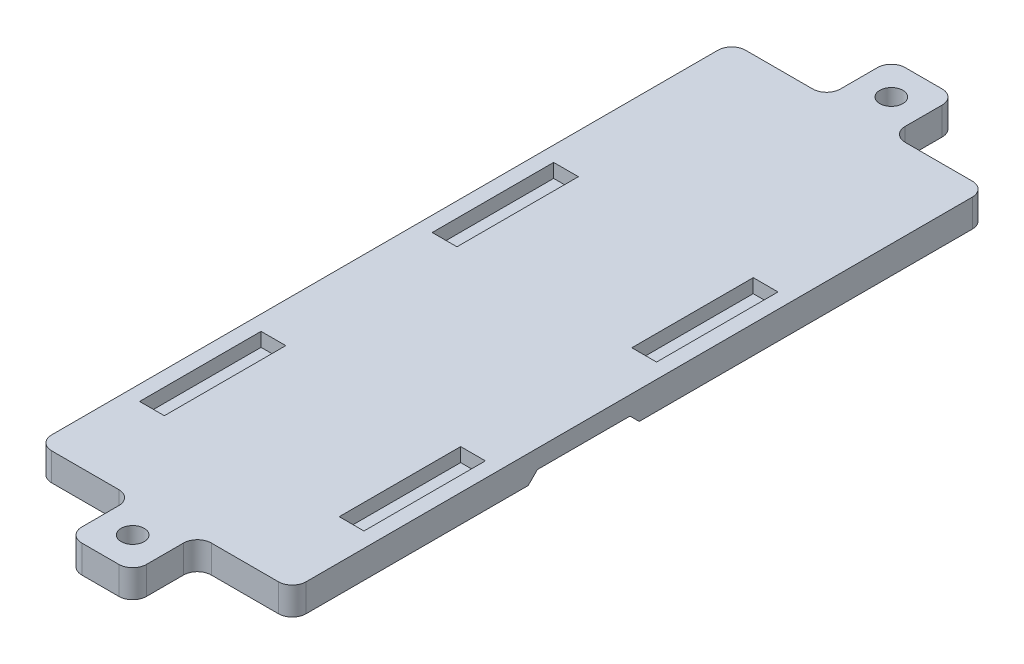
SolidWorks part; units mm, degrees
ref_plane "Ebene vorne" through (0, 0, 0) normal (0, 0, 1) x (1, 0, 0)
ref_plane "Ebene oben" through (0, 0, 0) normal (0, 1, 0) x (1, 0, 0)
ref_plane "Ebene rechts" through (0, 0, 0) normal (1, 0, 0) x (0, 0, -1)
sketch "Skizze1" plane through (0, 0, 0) normal (0, 1, 0) x (1, 0, 0)
  line L0 (0, 80.4105) -> (0, -85.1287) construction
  line L1 (-79.2647, 0) -> (92.6103, 0) construction
  line L2 (-27.5, -75) -> (-27.5, 75)
  line L3 (-27.5, 75) -> (-7, 75)
  line L4 (-7, 75) -> (-7, 89)
  line L5 (-7, 89) -> (7, 89)
  line L6 (7, 75) -> (7, 89)
  line L7 (27.5, 75) -> (7, 75)
  line L8 (27.5, -75) -> (27.5, 75)
  line L9 (27.5, -75) -> (7, -75)
  line L10 (7, -75) -> (7, -89)
  line L11 (-7, -89) -> (7, -89)
  line L12 (-7, -75) -> (-7, -89)
  line L13 (-27.5, -75) -> (-7, -75)
  circle A0 centre (0, 82) radius 2.5
  circle A1 centre (0, -82) radius 2.5
  point P11 (0, 89)
  point P14 (0, -89)
  point P16 (27.5, 0)
  point P21 (-27.5, 0)
  dimension "D6" = 5
  dimension "D1" = 55
  dimension "D2" = 150
  dimension "D3" = 14
  dimension "D4" = 14
  dimension "D5" = 7
extrude "Aufsatz-Linear austragen1" add sketch "Skizze1" along normal blind 6
sketch "Skizze2" plane through (0, 6, 0) normal (0, 1, 0) x (1, 0, 0)
  line L0 (-51.6965, 0) -> (56.2276, 0) construction
  line L1 (-24.25, 33.25) -> (-18.9, 33.25)
  line L2 (-24.25, 33.25) -> (-24.25, 7)
  line L3 (-24.25, 7) -> (-18.9, 7)
  line L4 (-18.9, 33.25) -> (-18.9, 7)
  line L5 (18.9, 33.25) -> (24.25, 33.25)
  line L6 (18.9, 33.25) -> (18.9, 7)
  line L7 (18.9, 7) -> (24.25, 7)
  line L8 (24.25, 33.25) -> (24.25, 7)
  line L9 (-24.25, -30) -> (-18.9, -30)
  line L10 (-24.25, -30) -> (-24.25, -56.25)
  line L11 (-24.25, -56.25) -> (-18.9, -56.25)
  line L12 (-18.9, -30) -> (-18.9, -56.25)
  line L13 (18.9, -30) -> (24.25, -30)
  line L14 (18.9, -30) -> (18.9, -56.25)
  line L15 (18.9, -56.25) -> (24.25, -56.25)
  line L16 (24.25, -30) -> (24.25, -56.25)
  line L17 (0, 62.4568) -> (0, -57.0695) construction
  dimension "D1" = 37.8
  dimension "D2" = 48.5
  dimension "D3" = 26.25
  dimension "D4" = 89.5
  dimension "D5" = 30
  dimension "D6" = 7
extrude "Schnitt-Linear austragen1" cut sketch "Skizze2" against normal blind 3
sketch "Skizze3" plane through (0, 0, 0) normal (0, -1, 0) x (1, 0, 0)
  line L1 (27.5, 2) -> (-27.5, 2)
  line L2 (27.5, 2) -> (27.5, 22)
  line L3 (27.5, 22) -> (-27.5, 22)
  line L4 (-27.5, 2) -> (-27.5, 22)
  line L5 (-27.5, -75) -> (-27.5, 75) construction
  dimension "D1" = 2
  dimension "D2" = 20
extrude "Schnitt-Linear austragen2" cut sketch "Skizze3" against normal blind 2
fillet "Verrundung1" radius 3 12 edges at (7, 3, -75) (7, 3, -89) (-7, 3, -89) (-7, 3, -75) (-7, 3, 75) (-7, 3, 89) (7, 3, 89) (7, 3, 75) (27.5, 3, 75) (-27.5, 3, 75) (27.5, 3, -75) (-27.5, 3, -75)
chamfer "Fase1" distance 2 angle 45 2 edges at (0, 0, 22) (0, 0, 2)
ref_axis "Achse1" through (0, -0.3, 0) along (0, 1, 0)
ref_axis "Achse2" through (0, 0, 97.9) along (0, 0, -1)
